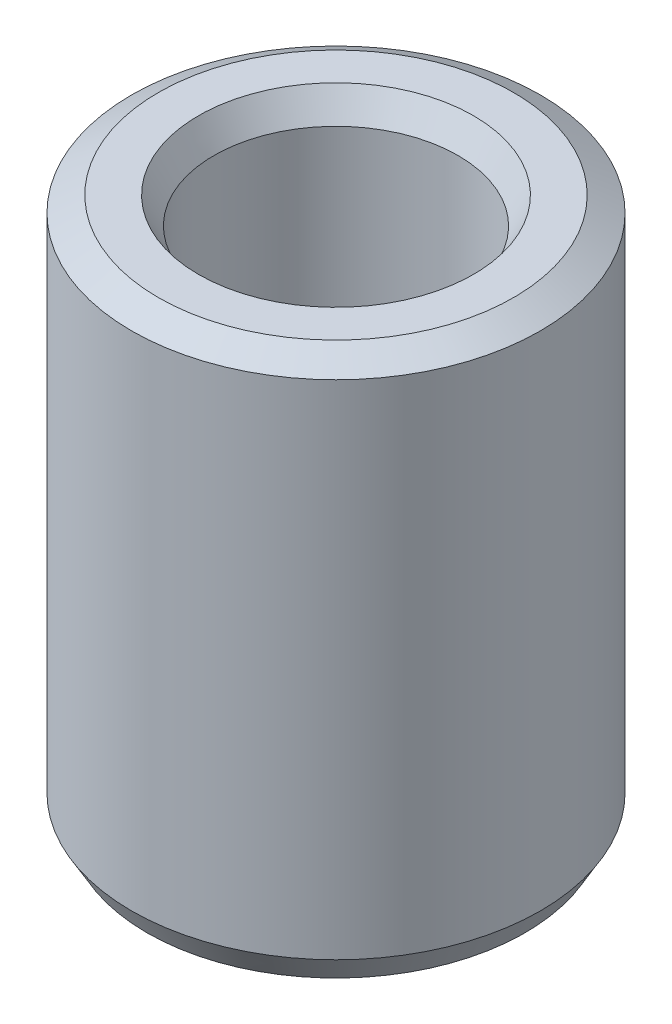
SolidWorks part; units mm, degrees
ref_plane "Front Plane" through (0, 0, 0) normal (0, 0, 1) x (1, 0, 0)
ref_plane "Top Plane" through (0, 0, 0) normal (0, 1, 0) x (1, 0, 0)
ref_plane "Right Plane" through (0, 0, 0) normal (1, 0, 0) x (0, 0, -1)
sketch "Sketch1" plane through (0, 0, 0) normal (0, 1, 0) x (1, 0, 0)
  circle A0 centre (0, 0) radius 10
  dimension "SLEEVE_OD" = 20
extrude "Boss-Extrude1" add sketch "Sketch1" along normal blind 26.6405
sketch "Sketch2" plane through (0, 0, 0) normal (0, 1, 0) x (1, 0, 0)
  circle A0 centre (0, 0) radius 5.9718
  dimension "BORE_D" = 11.9437
extrude "Cut-Extrude1" cut sketch "Sketch2" along normal through all
chamfer "Chamfer1" distance 0.7558 angle 60 4 edges at (0, 26.6405, 5.9718) (0, 0, 5.9718) (0, 0, 10) (0, 26.6405, 10) first distance on face at (0, 26.6405, 5.9718) first distance on face at (0, 0, 5.9718) first distance on face at (0, 26.6405, 10)
